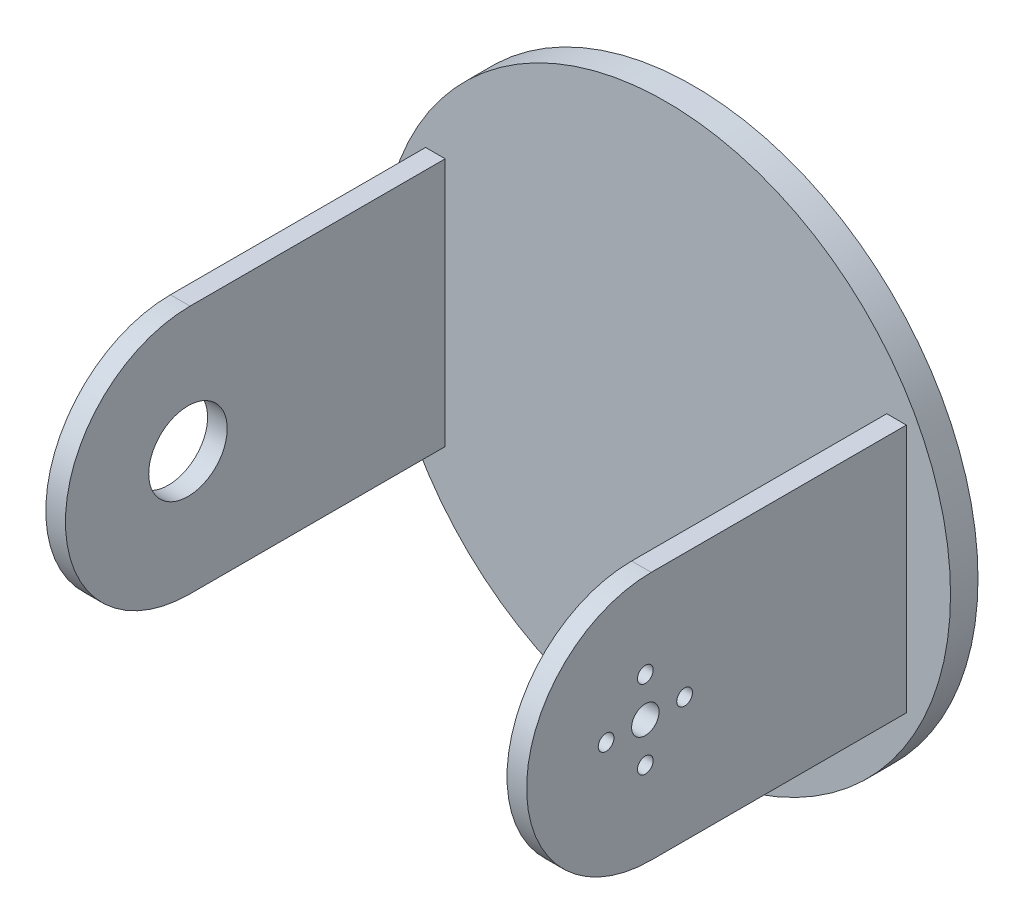
SolidWorks part; units mm, degrees
ref_plane "Front Plane" through (0, 0, 0) normal (0, 0, 1) x (1, 0, 0)
ref_plane "Top Plane" through (0, 0, 0) normal (0, 1, 0) x (1, 0, 0)
ref_plane "Right Plane" through (0, 0, 0) normal (1, 0, 0) x (0, 0, -1)
sketch "Sketch1" plane through (0, 0, 0) normal (0, 0, 1) x (1, 0, 0)
  line L0 (56.25, 31.75) -> (61.25, 31.75)
  line L1 (-56.25, 31.75) -> (56.25, 31.75)
  line L2 (-56.25, 31.75) -> (-56.25, -31.75)
  line L3 (-56.25, -31.75) -> (56.25, -31.75)
  line L4 (56.25, 31.75) -> (56.25, -31.75)
  line L5 (-56.25, 31.75) -> (56.25, -31.75) construction
  line L6 (-56.25, -31.75) -> (56.25, 31.75) construction
  line L7 (61.25, 31.75) -> (61.25, -31.75)
  line L8 (61.25, -31.75) -> (56.25, -31.75)
  line L9 (-56.25, 31.75) -> (-61.25, 31.75)
  line L10 (-61.25, 31.75) -> (-61.25, -31.75)
  line L11 (-61.25, -31.75) -> (-56.25, -31.75)
  circle A0 centre (0, 0) radius 72.5
  dimension "D1" = 145
  dimension "D2" = 63.5
  dimension "D3" = 112.5
  dimension "D4" = 5
  dimension "D5" = 5
extrude "Boss-Extrude1" add sketch "Sketch1" along normal blind 65 contours L2 L11 L10 L9 | L0 L7 L8 L4
extrude "Boss-Extrude2" add sketch "Sketch1<4>" against normal blind 7 contours A0
sketch "Sketch1<4>" plane through (0, 0, 0) normal (0, 0, 1) x (1, 0, 0) same geometry as "Sketch1"
sketch "Sketch2" plane through (56.25, 0, 0) normal (-1, 0, 0) x (0, 0, 1)
  line L0 (65, 31.75) -> (65, -31.75) construction
  line L1 (65, -31.75) -> (65, 31.75)
  arc A0 (65, -31.75) -> (65, 31.75) centre (65, 0) ccw
extrude "Boss-Extrude3" add sketch "Sketch2" against normal blind 5
sketch "Sketch3" plane through (-56.25, 0, 0) normal (1, 0, 0) x (0, 0, -1)
  line L0 (-65, 31.75) -> (-65, -31.75) construction
  line L1 (-65, 31.75) -> (-65, -31.75)
  arc A0 (-65, 31.75) -> (-65, -31.75) centre (-65, 0) ccw
extrude "Boss-Extrude4" add sketch "Sketch3" against normal blind 5
sketch "Sketch4" plane through (0, 0, -7) normal (0, 0, -1) x (-1, 0, 0)
  circle A0 centre (0, 0) radius 30
  dimension "D1" = 60
extrude "Boss-Extrude5" add sketch "Sketch4" along normal blind 7
sketch "Sketch5" plane through (0, 0, -14) normal (0, 0, -1) x (-1, 0, 0)
  circle A0 centre (0, 0) radius 32
  dimension "D1" = 64
extrude "Boss-Extrude6" add sketch "Sketch5" along normal blind 2
sketch "Sketch6" plane through (0, 0, -16) normal (0, 0, -1) x (-1, 0, 0)
  circle A0 centre (0, 0) radius 10
  dimension "D1" = 20
extrude "Boss-Extrude7" add sketch "Sketch6" along normal blind 17
sketch "Sketch8" plane through (-61.25, 0, 0) normal (-1, 0, 0) x (0, 0, 1)
  circle A0 centre (38.0908, 0) radius 3.5
  circle A1 centre (38.0908, 0) radius 10.585
  circle A2 centre (48.6758, 0) radius 2
  circle A3 centre (38.0908, -10.585) radius 2
  circle A4 centre (38.0908, 10.585) radius 2
  circle A5 centre (27.5058, 0) radius 2
  dimension "D1" = 7
  dimension "D2" = 21.17
  dimension "D3" = 4
  dimension "D4" = 4
  dimension "D5" = 4
  dimension "D6" = 4
sketch "Sketch9" plane through (56.25, 0, 0) normal (-1, 0, 0) x (0, 0, 1)
  circle A0 centre (65, 0) radius 10
  dimension "D1" = 20
sketch "Sketch11" plane through (-61.25, 0, 0) normal (-1, 0, 0) x (0, 0, 1)
  circle A0 centre (45.9799, 0) radius 10
  dimension "D1" = 20
sketch "Sketch13" plane through (61.25, 0, 0) normal (1, 0, 0) x (0, 0, -1)
  circle A0 centre (-66.506, 0) radius 3.5
  circle A1 centre (-66.506, 0) radius 10
  circle A2 centre (-76.506, 0) radius 2
  circle A3 centre (-66.506, -10) radius 2
  circle A4 centre (-56.506, 0) radius 2
  circle A5 centre (-66.506, 10) radius 2
  dimension "D1" = 7
  dimension "D2" = 20
  dimension "D3" = 4
  dimension "D4" = 4
  dimension "D5" = 4
  dimension "D6" = 4
extrude "Cut-Extrude3" cut sketch "Sketch13" against normal up to surface (5 mm away) contours A5 | A4 | A0 | A3 | A2 up to face at (56.25, 0, 40.4375)
sketch "Sketch14" plane through (-61.25, 0, 0) normal (-1, 0, 0) x (0, 0, 1)
  circle A0 centre (65.5309, 0) radius 10
  dimension "D1" = 20
extrude "Cut-Extrude4" cut sketch "Sketch14" against normal up to surface (5 mm away) up to face at (-56.25, 0, 40.4375)
